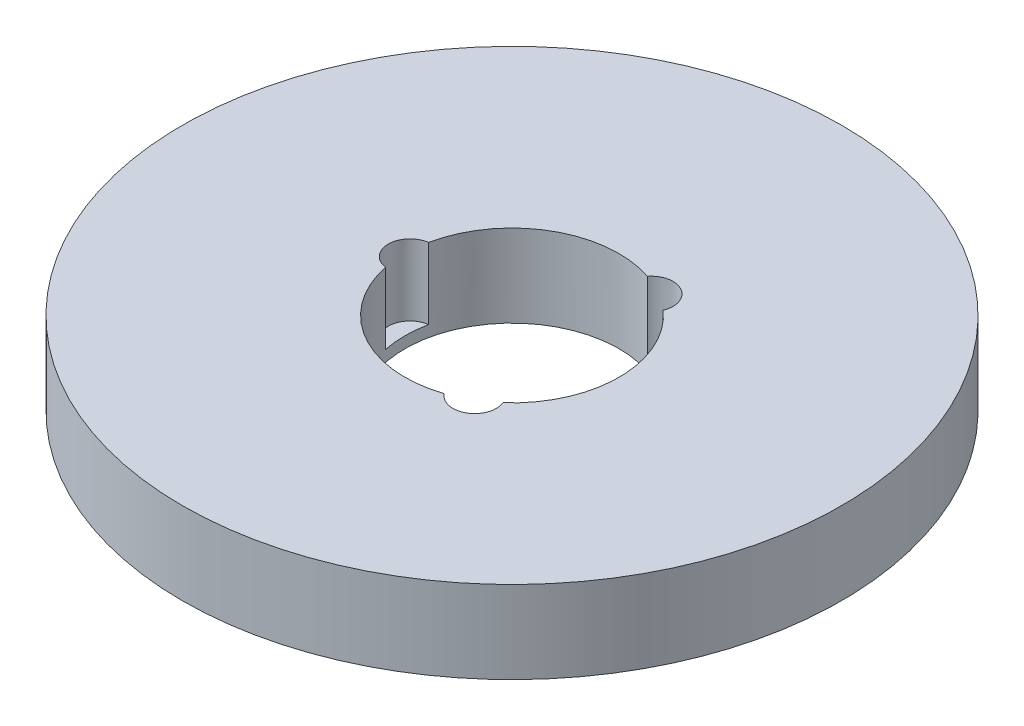
SolidWorks part; units mm, degrees
ref_plane "Front Plane" through (0, 0, 0) normal (0, 0, 1) x (1, 0, 0)
ref_plane "Top Plane" through (0, 0, 0) normal (0, 1, 0) x (1, 0, 0)
ref_plane "Right Plane" through (0, 0, 0) normal (1, 0, 0) x (0, 0, -1)
sketch "Sketch1" plane through (0, 0, 0) normal (0, 1, 0) x (1, 0, 0)
  circle A0 centre (0, 0) radius 100
  dimension "FLANGE_OD" = 200
extrude "Boss-Extrude1" add sketch "Sketch1" along normal blind 25
sketch "Sketch2" plane through (0, 0, 0) normal (0, 1, 0) x (1, 0, 0)
  circle A0 centre (0, 0) radius 32.5
  dimension "BORE_D" = 65
extrude "Cut-Extrude1" cut sketch "Sketch2" along normal through all
sketch "Sketch3" plane through (0, 25, 0) normal (0, 1, 0) x (1, 0, 0)
  circle A0 centre (0, 0) radius 30.9519 construction
  circle A1 centre (-30.9519, 0) radius 6.5856
  dimension "BOLT_D" = 13.1711
  dimension "BOLT_PCD" = 61.9038
extrude "Cut-Extrude2" cut sketch "Sketch3" against normal blind 21.5873
pattern_circular "CirPattern1" count 3 over 360 about axis through (0, 0, 0) along (0, 1, 0) of "Cut-Extrude2"
